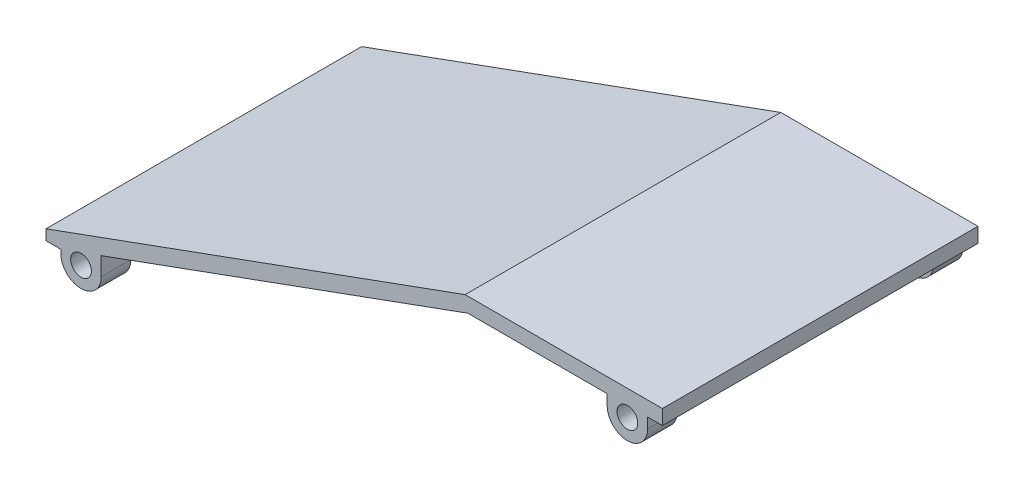
SolidWorks part; units mm, degrees
ref_plane "Спереди" through (0, 0, 0) normal (0, 0, 1) x (1, 0, 0)
ref_plane "Сверху" through (0, 0, 0) normal (0, 1, 0) x (1, 0, 0)
ref_plane "Справа" through (0, 0, 0) normal (1, 0, 0) x (0, 0, -1)
sketch "Эскиз1" plane through (0, 0, 0) normal (0, 0, 1) x (1, 0, 0)
  line L0 (14.279, 76) -> (13.2529, 78.8191) construction
  line L1 (53.75, 79) -> (13.75, 79)
  line L2 (13.75, 79) -> (-71.25, 48.0625)
  line L3 (-71.25, 48.0625) -> (-71.25, 45.9619)
  line L4 (-71.25, 45.9619) -> (-68.25, 45.9619)
  line L5 (-68.25, 45.9619) -> (14.279, 76)
  line L6 (14.279, 76) -> (53.75, 76)
  line L7 (53.75, 76) -> (53.75, 79)
  line L8 (-68.25, 45.9619) -> (-69.2761, 48.781) construction
  line L10 (53.75, -6) -> (53.75, 76) construction
  line L11 (53.75, 76) -> (50.75, 76) construction
  line L12 (-71.25, 45.9619) -> (-71.25, -6) construction
  point P12 (19.4421, 81.2951)
  point P15 (18.6481, 79)
  point P16 (-62.9245, 49.5395)
  point P19 (-68.2631, 43.6816)
  point P20 (-68.76, 46.4944)
  point P21 (0, 0)
  point P22 (0, 0)
  point P24 (-69.2761, 48.9879)
  dimension "D1" = 3
  dimension "D2" = 20
  dimension "D3" = 40
extrude "Бобышка-Вытянуть1" add sketch "Эскиз1" along normal mid plane 64
sketch "Эскиз2" plane through (0, 0, 0) normal (0, 0, 1) x (1, 0, 0)
  line L2 (42.55, 79) -> (42.55, 73.9)
  line L4 (50.75, 76) -> (50.75, -3) construction
  line L5 (50.75, 73.9) -> (50.75, 79)
  line L6 (53.75, 79) -> (13.75, 79) construction
  line L7 (50.75, 79) -> (42.55, 79)
  line L9 (-60.05, 52.139) -> (-60.05, 45.2194)
  line L10 (13.75, 79) -> (-71.25, 48.0625) construction
  line L11 (-68.25, -3) -> (-68.25, 45.9619) construction
  line L12 (-68.25, 45.2194) -> (-68.25, 49.1544)
  line L13 (-68.25, 49.1544) -> (-60.05, 52.139)
  arc A0 (42.55, 73.9) -> (50.75, 73.9) centre (46.65, 73.9) ccw
  circle A1 centre (46.65, 73.9) radius 2.1
  arc A2 (-60.05, 45.2194) -> (-68.25, 45.2194) centre (-64.15, 45.2194) cw
  circle A3 centre (-64.15, 45.2194) radius 2.1
  point P2 (-68.25, 41.9569)
  dimension "D1" = 4.2
  dimension "D2" = 2
  dimension "D3" = 3
  dimension "D4" = 2
  dimension "D5" = 3
extrude "Бобышка-Вытянуть2" add sketch "Эскиз2" against normal blind 6 from surface contours L2 A0 L5 L7 A1 | A1 | A2 L9 L13 L12 A3 | A3 region at (46.65, 78.8768, 0) region at (-60.1874, 48.6792, 0) region at (46.65, 73.9, 0) region at (-64.15, 45.2194, 0) starting at face at (-10.7459, 64.2838, 32)
extrude "Бобышка-Вытянуть3" add sketch "Эскиз2<3>" along normal blind 6 from surface contours A1 | L2 A0 L5 L7 A1 | A2 L9 L13 L12 A3 | A3 region at (46.65, 78.8768, 0) region at (-60.1874, 48.6792, 0) region at (46.65, 73.9, 0) region at (-64.15, 45.2194, 0) starting at face at (-10.7459, 64.2838, -32)
sketch "Эскиз2<3>" plane through (0, 0, 0) normal (0, 0, 1) x (1, 0, 0) same geometry as "Эскиз2"
extrude "Вырез-Вытянуть1" cut sketch "Эскиз2<4>" against normal blind 4 from surface contours A1 | A3 region at (46.65, 73.9, 0) region at (-64.15, 45.2194, 0) starting at face at (-5.4979, 62.9265, 32)
sketch "Эскиз2<4>" plane through (0, 0, 0) normal (0, 0, 1) x (1, 0, 0) same geometry as "Эскиз2"
extrude "Вырез-Вытянуть2" cut sketch "Эскиз2<5>" along normal blind 4 from surface contours A1 | A3 region at (46.65, 73.9, 0) region at (-64.15, 45.2194, 0) starting at face at (-5.4979, 62.9265, -32)
sketch "Эскиз2<5>" plane through (0, 0, 0) normal (0, 0, 1) x (1, 0, 0) same geometry as "Эскиз2"
